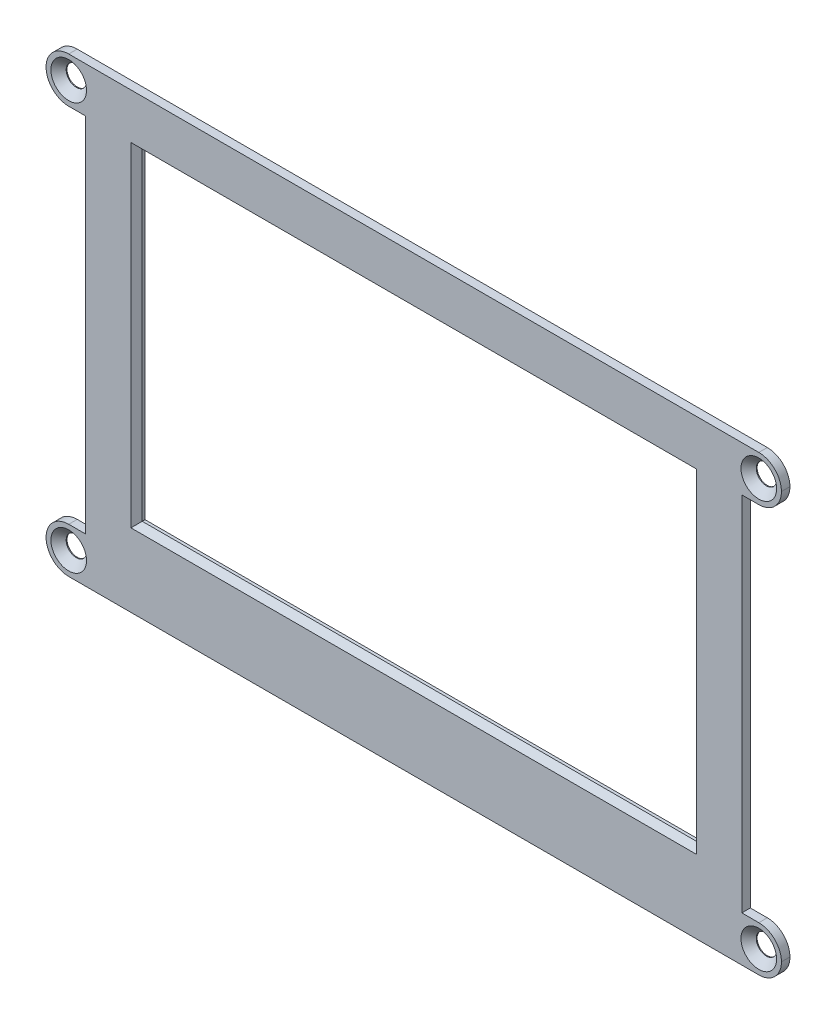
SolidWorks part; units mm, degrees
ref_plane "Front Plane" through (0, 0, 0) normal (0, 0, 1) x (1, 0, 0)
ref_plane "Top Plane" through (0, 0, 0) normal (0, 1, 0) x (1, 0, 0)
ref_plane "Right Plane" through (0, 0, 0) normal (1, 0, 0) x (0, 0, -1)
sketch "Sketch1" plane through (0, 0, 0) normal (0, 0, 1) x (1, 0, 0)
  line L1 (-65, 40) -> (65, 40)
  line L2 (-65, 40) -> (-65, -40)
  line L3 (-65, -40) -> (65, -40)
  line L4 (65, 40) -> (65, -40)
  line L5 (-65, 40) -> (65, -40) construction
  line L6 (-65, -40) -> (65, 40) construction
  point P0 (0, 0)
  dimension "D1" = 130
  dimension "D2" = 80
extrude "Boss-Extrude1" add sketch "Sketch1" along normal blind 1.5
fillet "Fillet1" radius 4 4 edges at (65, -40, 0.75) (-65, -40, 0.75) (65, 40, 0.75) (-65, 40, 0.75)
hole_wizard "CSK for M3 Flat Countersunk Head Screw1" positions "Sketch2" profile "Sketch3" countersink size "M3" standard "JIS" end condition through all
sketch "Sketch2" plane through (0, 0, 1.5) normal (0, 0, 1) x (1, 0, 0)
  line L0 (61, 40) -> (-61, 40) construction
  line L1 (-65, 36) -> (-65, -36) construction
  point P0 (-61, 36)
  dimension "D1" = 4
  dimension "D2" = 4
sketch "Sketch3" plane through (-61, 36, 1.5) normal (1, 0, 0) x (0, -1, 0)
  line L0 (0, 0) -> (0, 1.5)
  line L1 (0, 1.5) -> (1.8, 1.5)
  line L2 (1.8, 1.5) -> (1.8, 1.35)
  line L3 (1.8, 1.35) -> (3.15, 0)
  line L5 (3.15, 0) -> (0, 0)
  line L6 (-1.8, 1.35) -> (-3.15, 0) construction
  line L11 (0, -6.35) -> (0, 107.95) construction
  dimension "Thru Hole Dia." = 3.6
  dimension "Thru Hole Depth" = 1.5
  dimension "Near C'Sink Dia." = 6.3
  dimension "Near C'Sink Angle" = 90
mirror "Mirror1" about plane through (0, 0, 0) normal (1, 0, 0) of "CSK for M3 Flat Countersunk Head Screw1"
mirror "Mirror2" about plane through (0, 0, 0) normal (0, 1, 0) of "Mirror1", "CSK for M3 Flat Countersunk Head Screw1"
sketch "Sketch4" plane through (0, 0, 1.5) normal (0, 0, 1) x (1, 0, 0)
  line L1 (49, 30.95) -> (-49, 30.95)
  line L2 (49, 30.95) -> (49, -26.05)
  line L3 (49, -26.05) -> (-49, -26.05)
  line L4 (-49, 30.95) -> (-49, -26.05)
  line L5 (49, 30.95) -> (-49, -26.05) construction
  line L6 (49, -26.05) -> (-49, 30.95) construction
  point P10 (0, 2.45)
  dimension "D1" = 98
  dimension "D2" = 57
  dimension "D3" = 2.45
  dimension "D4" = 0
extrude "Cut-Extrude1" cut sketch "Sketch4" against normal blind 6
sketch "Sketch6" plane through (0, 0, 1.5) normal (0, 0, 1) x (1, 0, 0)
  line L0 (65, -36) -> (65, 36) construction
  line L1 (58, 32) -> (65, 32)
  line L2 (58, 32) -> (58, -32)
  line L3 (58, -32) -> (65, -32)
  line L4 (65, 32) -> (65, -32)
  line L5 (61, 40) -> (-61, 40) construction
  line L6 (-61, -40) -> (61, -40) construction
  dimension "D1" = 7
  dimension "D2" = 0
  dimension "D3" = 8
  dimension "D4" = 8
extrude "Cut-Extrude3" cut sketch "Sketch6" against normal blind 10
mirror "Mirror6" about plane through (0, 0, 0) normal (1, 0, 0) of "Cut-Extrude3"
fillet "Fillet3" radius 4 4 edges at (65, -32, 0.75) (65, 32, 0.75) (-65, -32, 0.75) (-65, 32, 0.75)
chamfer "Chamfer1" distance 1 angle 45 4 edges at (-49, 2.45, 1.5) (0, 30.95, 1.5) (49, 2.45, 1.5) (0, -26.05, 1.5)
